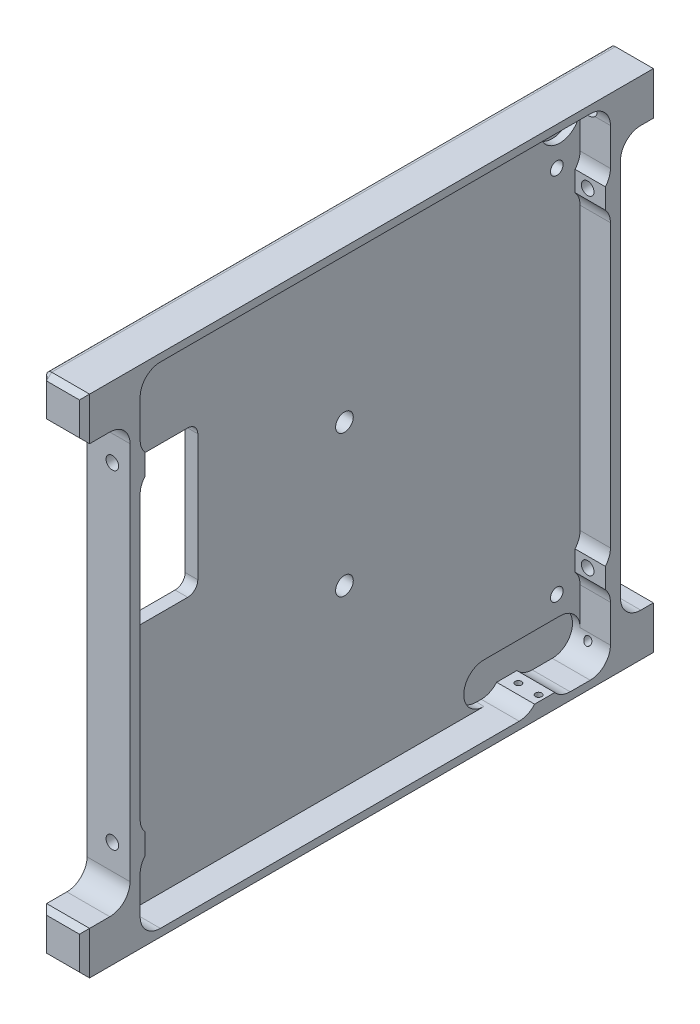
SolidWorks part; units mm, degrees
material "6061-T6 (SS)"
ref_plane "Front" through (0, 0, 0) normal (0, 0, 1) x (1, 0, 0)
ref_plane "Top" through (0, 0, 0) normal (0, 1, 0) x (1, 0, 0)
ref_plane "Right" through (0, 0, 0) normal (1, 0, 0) x (0, 0, -1)
sketch "Sketch1" plane through (0, 0, 0) normal (1, 0, 0) x (0, 0, -1)
  line L1 (0, 0) -> (-113.5, 0)
  line L2 (0, 0) -> (0, 100)
  line L3 (0, 100) -> (-113.5, 100)
  line L4 (-113.5, 0) -> (-113.5, 100)
  line L5 (-113.5, 91.5) -> (-104.5, 91.5)
  line L6 (-113.5, 91.5) -> (-113.5, 8.5)
  line L7 (-113.5, 8.5) -> (-104.5, 8.5)
  line L8 (-104.5, 91.5) -> (-104.5, 8.5)
  line L9 (0, 91.5) -> (-7.5, 91.5)
  line L10 (0, 91.5) -> (0, 8.5)
  line L11 (0, 8.5) -> (-7.5, 8.5)
  line L12 (-7.5, 91.5) -> (-7.5, 8.5)
  line L13 (-96.5, 91.5) -> (-15.5, 91.5)
  line L14 (-96.5, 91.5) -> (-96.5, 8.5)
  line L15 (-96.5, 8.5) -> (-15.5, 8.5)
  line L16 (-15.5, 91.5) -> (-15.5, 8.5)
  dimension "D1" = 113.5
  dimension "D2" = 100
  dimension "D3" = 8.5
  dimension "D4" = 8.5
  dimension "D5" = 8
  dimension "D6" = 8
  dimension "D7" = 9
  dimension "D8" = 7.5
extrude "Body" add sketch "Sketch1" along normal blind 8.5 contours L12 L9 L2 L3 L4 L5 L8 L7 L1 L11 L13 L16 L15 L14
fillet "RailFillet" radius 1 2 edges at (0, 0, 56.75) (0, 100, 56.75)
chamfer "FootChamfer" distance 1 angle 45 20 edges at (4.75, 0, 0) (8.5, 4.25, 0) (4.25, 8.5, 0) (0, 4.75, 0) (4.25, 91.5, 0) (8.5, 95.75, 0) (4.75, 100, 0) (0, 95.25, 0) (4.75, 100, 113.5) (8.5, 95.75, 113.5) (4.25, 91.5, 113.5) (0, 95.25, 113.5) (4.25, 8.5, 113.5) (8.5, 4.25, 113.5) (4.75, 0, 113.5) (0, 4.75, 113.5) (0.2929, 0.2929, 0) (0.2929, 99.7071, 0) (0.2929, 99.7071, 113.5) (0.2929, 0.2929, 113.5)
sketch "Sketch5" plane through (8.5, 0, 0) normal (1, 0, 0) x (0, 0, -1)
  line L1 (-96.5, 91.5) -> (-15.5, 91.5)
  line L2 (-96.5, 91.5) -> (-96.5, 8.5)
  line L3 (-96.5, 8.5) -> (-15.5, 8.5)
  line L4 (-15.5, 91.5) -> (-15.5, 8.5)
extrude "Boss-Extrude3" add sketch "Sketch5" against normal up to surface (8.5 mm away) up to face at (0, 50, 56.5)
sketch "Sketch6" plane through (8.5, 0, 0) normal (1, 0, 0) x (0, 0, -1)
  line L0 (-1, 100) -> (-112.5, 100) construction
  line L1 (-102.5, 98.5) -> (-9.5, 98.5)
  line L2 (-102.5, 98.5) -> (-102.5, 1.5)
  line L3 (-102.5, 1.5) -> (-9.5, 1.5)
  line L4 (-9.5, 98.5) -> (-9.5, 1.5)
  line L5 (-1, 0) -> (-112.5, 0) construction
  line L7 (-7.5, 91.5) -> (-7.5, 8.5) construction
  line L10 (-104.5, 91.5) -> (-104.5, 8.5) construction
  dimension "D1" = 1.5
  dimension "D2" = 1.5
  dimension "D3" = 2
  dimension "D4" = 2
extrude "Cut-Extrude3" cut sketch "Sketch6" against normal offset from surface (6 mm away) 2.5 up to face at (0, 50, 56.5)
sketch "Sketch4" plane through (8.5, 0, 0) normal (1, 0, 0) x (0, 0, -1)
  line L1 (-92.5, 90) -> (-19.5, 90)
  line L2 (-92.5, 90) -> (-92.5, 10)
  line L3 (-92.5, 10) -> (-19.5, 10)
  line L4 (-19.5, 90) -> (-19.5, 10)
  line L6 (-7.5, 91.5) -> (-7.5, 8.5) construction
  line L8 (-1, 100) -> (-112.5, 100) construction
  line L9 (-1, 0) -> (-112.5, 0) construction
  line L10 (-104.5, 91.5) -> (-104.5, 8.5) construction
  dimension "D1" = 12
  dimension "D2" = 10
  dimension "D3" = 10
  dimension "D4" = 12
ref_plane "Plane1" through (0, 50, 0) normal (0, 1, 0) x (1, 0, 0)
ref_plane "Plane2" through (0, 0, 56) normal (0, 0, -1) x (-1, 0, 0)
sketch "Sketch21" plane through (0, 0, 0) normal (1, 0, 0) x (0, 0, -1)
  line L0 (-98.1, 86.5) -> (-98.1, 13.5) construction
  line L1 (-98.1, 13.5) -> (-14.1, 13.5) construction
  line L2 (-14.1, 13.5) -> (-14.1, 86.5) construction
  line L3 (-14.1, 86.5) -> (-98.1, 86.5) construction
  line L4 (-14.1, 50) -> (-7.5, 50) construction
  line L6 (-7.5, 91.5) -> (-7.5, 8.5) construction
  line L7 (0, 99) -> (0, 92.5) construction
  line L8 (-14.1, 50) -> (-98.1, 50) construction
  line L9 (-56.1, 50) -> (-56.1, 36) construction
  line L10 (-7.5, 50) -> (-7.5, 0) construction
  line L11 (-112.5, 0) -> (-1, 0) construction
  line L12 (-1, 100) -> (-112.5, 100) construction
  line L13 (-7.5, 100) -> (-7.5, 50) construction
  line L16 (-56.1, 64) -> (-56.1, 50) construction
  point P3 (-14.1, 13.5)
  point P5 (-98.1, 86.5)
  point P7 (-98.1, 13.5)
  point P11 (-56.1, 36)
  point P25 (-14.1, 86.5)
  point P26 (-56.1, 64)
  dimension "D3" = 28
  dimension "D1" = 73
  dimension "D2" = 84
  dimension "D4" = 14.1
sketch "Sketch29" plane through (0, 0, 0) normal (0, 0, -1) x (-1, 0, 0)
  line L0 (-1, 92.5) -> (-7.5, 99)
  line L1 (-7.5, 99) -> (-1, 99)
  line L2 (-1, 99) -> (-4.25, 95.75)
hole_wizard "#8-36 Tapped Hole1" positions "Sketch30" profile "Sketch31" tap size "#8-36" standard "ANSI Inch"
sketch "Sketch30" plane through (0, 0, 0) normal (0, 0, -1) x (-1, 0, 0)
  point P0 (-4.25, 95.75)
sketch "Sketch31" plane through (4.25, 95.75, 0) normal (1, 0, 0) x (0, 1, 0)
  line L0 (0, 0) -> (0, 14.5878)
  line L1 (0, 14.5878) -> (1.7272, 13.55)
  line L2 (1.7272, 13.55) -> (1.7272, 0)
  line L5 (1.7272, 0) -> (0, 0)
  line L10 (0, 14.5878) -> (-1.7272, 13.55) construction
  line L11 (0, -6.35) -> (0, 107.95) construction
  dimension "Tap Drill Dia." = 3.4544
  dimension "Tap Drill Depth" = 13.55
  dimension "Drill Angle" = 118
cosmetic thread "Hole Thread1" parameters "D1"=10.5229, "D2"=4.1656
sketch "Sketch32" plane through (0, 0, 0) normal (0, 0, -1) x (-1, 0, 0)
  line L1 (-4.25, 1) -> (-4.25, 4.25) construction
  line L2 (-7.5, 1) -> (-1, 1) construction
  line L3 (-4.25, 4.25) -> (-7.5, 4.25) construction
  line L4 (-7.5, 7.5) -> (-7.5, 1) construction
  point P1 (-4.25, 4.25)
hole_wizard "#8-36 Tapped Hole2" [suppressed] positions "Sketch33" profile "Sketch34" tap size "#8-36" standard "ANSI Inch"
sketch "Sketch33" plane through (0, 0, 0) normal (0, 0, -1) x (-1, 0, 0)
  point P0 (-4.25, 4.25)
sketch "Sketch34" plane through (4.25, 4.25, 0) normal (1, 0, 0) x (0, 1, 0)
  line L0 (0, 0) -> (0, 11.4878)
  line L1 (0, 11.4878) -> (1.7272, 10.45)
  line L2 (1.7272, 10.45) -> (1.7272, 0)
  line L5 (1.7272, 0) -> (0, 0)
  line L10 (0, 11.4878) -> (-1.7272, 10.45) construction
  line L11 (0, -6.35) -> (0, 107.95) construction
  dimension "Tap Drill Dia." = 3.4544
  dimension "Tap Drill Depth" = 10.45
  dimension "Drill Angle" = 118
cosmetic thread "Hole Thread2" [suppressed] parameters "D1"=8.33, "D2"=4.1656
sketch "Sketch44" [suppressed] plane through (2.5, 0, 0) normal (1, 0, 0) x (0, 0, -1)
  point P0 (-17.45, 3.7)
  point P2 (-17.45, 7.7)
sketch "Sketch57" plane through (2.5, 0, 0) normal (1, 0, 0) x (0, 0, -1)
  line L0 (-9.5, 1.5) -> (-9.5, 98.5) construction
  line L1 (-9.5, 84.5) -> (-10.5, 84.5)
  line L2 (-9.5, 84.5) -> (-9.5, 80.5)
  line L3 (-9.5, 80.5) -> (-10.5, 80.5)
  line L4 (-10.5, 84.5) -> (-10.5, 80.5)
  line L5 (-102.5, 1.5) -> (-102.5, 98.5) construction
  line L6 (-9.5, 19.5) -> (-10.5, 19.5)
  line L7 (-9.5, 19.5) -> (-9.5, 15.5)
  line L8 (-9.5, 15.5) -> (-10.5, 15.5)
  line L9 (-10.5, 19.5) -> (-10.5, 15.5)
  line L10 (-10.5, 19.5) -> (-101.5, 19.5)
  line L11 (-10.5, 19.5) -> (-10.5, 15.5)
  line L12 (-10.5, 15.5) -> (-101.5, 15.5)
  line L13 (-101.5, 19.5) -> (-101.5, 15.5)
  line L14 (-10.5, 84.5) -> (-101.5, 84.5)
  line L15 (-10.5, 84.5) -> (-10.5, 80.5)
  line L16 (-10.5, 80.5) -> (-101.5, 80.5)
  line L17 (-101.5, 84.5) -> (-101.5, 80.5)
  line L18 (-101.5, 84.5) -> (-102.5, 84.5)
  line L19 (-101.5, 84.5) -> (-101.5, 80.5)
  line L20 (-101.5, 80.5) -> (-102.5, 80.5)
  line L21 (-102.5, 84.5) -> (-102.5, 80.5)
  line L22 (-9.5, 50) -> (-102.5, 50) construction
  line L23 (-101.5, 19.5) -> (-102.5, 19.5)
  line L24 (-101.5, 19.5) -> (-101.5, 15.5)
  line L25 (-101.5, 15.5) -> (-102.5, 15.5)
  line L26 (-102.5, 19.5) -> (-102.5, 15.5)
  line L28 (-102.5, 82.5) -> (-102.5, 50) construction
  line L29 (-102.5, 50) -> (-102.5, 17.5) construction
  line L31 (-9.5, 98.5) -> (-9.5, 1.5) construction
  dimension "D1" = 4
  dimension "D2" = 4
  dimension "D3" = 1
  dimension "D4" = 32.5
  dimension "D5" = 32.5
extrude "Boss-Extrude24" add sketch "Sketch57" along normal up to surface (6 mm away) contours L18 L21 L20 L17 | L23 L26 L25 L13 | L6 L9 L8 L7 | L1 L4 L3 L2 up to face at (8.5, 50, 56)
fillet "Fillet5" radius 4 8 edges at (5.5, 84.5, 102.5) (5.5, 19.5, 102.5) (5.5, 80.5, 102.5) (5.5, 15.5, 102.5) (5.5, 19.5, 9.5) (5.5, 15.5, 9.5) (5.5, 80.5, 9.5) (5.5, 84.5, 9.5)
sketch "Sketch59" plane through (0, 0, 7.5) normal (0, 0, -1) x (-1, 0, 0)
  line L0 (-5, 91.5) -> (-5, 82.5) construction
  line L2 (-5, 82.5) -> (-5, 17.5) construction
  line L3 (-5, 17.5) -> (-5, 8.5) construction
  line L5 (0, 91.5) -> (0, 8.5) construction
  line L6 (-8.5, 91.5) -> (0, 91.5) construction
  line L7 (-8.5, 8.5) -> (0, 8.5) construction
  dimension "D1" = 65
  dimension "D2" = 5
hole_wizard "M3x0.5 Tapped Hole1" positions "Sketch60" profile "Sketch61" tap size "M3x0.5" standard "ANSI Metric" end condition through all
sketch "Sketch60" plane through (0, 0, 7.5) normal (0, 0, -1) x (-1, 0, 0)
  point P0 (-5, 82.5)
  point P3 (-5, 17.5)
sketch "Sketch61" plane through (5, 82.5, 7.5) normal (1, 0, 0) x (0, 1, 0)
  line L0 (0, 0) -> (0, 106)
  line L1 (0, 106) -> (1.25, 106)
  line L2 (1.25, 106) -> (1.25, 0)
  line L5 (1.25, 0) -> (0, 0)
  line L11 (0, -6.35) -> (0, 107.95) construction
  dimension "Thru Tap Drill Dia." = 2.5
  dimension "Thru Tap Drill Depth" = 106
cosmetic thread "Hole Thread5" parameters "D2"=3
cosmetic thread "Hole Thread6" parameters "D2"=3
sketch "Sketch62" [suppressed] plane through (1, 0, 0) normal (1, 0, 0) x (0, 0, -1)
  line L1 (-11.25, 13.5) -> (-11.25, 1.5)
  line L2 (-11.5, 1.5) -> (-100, 1.5) construction
  line L3 (-11.25, 1.5) -> (-15.75, 1.5)
  line L4 (-15.75, 1.5) -> (-15.75, 10.1459)
  circle A0 centre (-14.75, 86.5) radius 3.5
  circle A1 centre (-14.75, 13.5) radius 3.5
  circle A2 centre (-97.75, 13.5) radius 3.5
  circle A3 centre (-97.75, 86.5) radius 3.5
  circle A4 centre (-97.75, 86.5) radius 1.25 construction
  circle A5 centre (-97.75, 13.5) radius 1.25 construction
  circle A6 centre (-14.75, 13.5) radius 1.25 construction
  circle A7 centre (-14.75, 86.5) radius 1.25 construction
  circle A8 centre (-97.75, 86.5) radius 1.25
  circle A9 centre (-97.75, 13.5) radius 1.25
  circle A10 centre (-14.75, 13.5) radius 1.25
  circle A11 centre (-14.75, 86.5) radius 1.25
  dimension "D1" = 7
  dimension "D2" = 4.5
fillet "Fillet7" radius 4 4 edges at (5.5, 98.5, 102.5) (5.5, 1.5, 102.5) (5.5, 1.5, 9.5) (5.5, 98.5, 9.5)
hole_wizard "M3x0.5 Tapped Hole2" positions "Sketch67" profile "Sketch68" tap size "M3x0.5" standard "ANSI Metric"
sketch "Sketch67" plane through (0, 0, 0) normal (-1, 0, 0) x (0, 0, 1)
  point P0 (14.1, 13.5)
  point P3 (14.1, 86.5)
  point P12 (98.1, 86.5)
  point P15 (98.1, 13.5)
  point P19 (0, 0)
  point P20 (0, 0)
sketch "Sketch68" plane through (0, 13.5, 14.1) normal (0, 1, 0) x (0, 0, 1)
  line L0 (0, 0) -> (0, 8.2511)
  line L1 (0, 8.2511) -> (1.25, 7.5)
  line L2 (1.25, 7.5) -> (1.25, 0)
  line L5 (1.25, 0) -> (0, 0)
  line L10 (0, 8.2511) -> (-1.25, 7.5) construction
  line L11 (0, -6.35) -> (0, 107.95) construction
  dimension "Tap Drill Dia." = 2.5
  dimension "Tap Drill Depth" = 7.5
  dimension "Drill Angle" = 118
cosmetic thread "Hole Thread17" parameters "D1"=2.5, "D2"=3
cosmetic thread "Hole Thread18" parameters "D1"=2.5, "D2"=3
cosmetic thread "Hole Thread21" parameters "D1"=2.5, "D2"=3
cosmetic thread "Hole Thread22" parameters "D1"=2.5, "D2"=3
fillet "Fillet8" radius 4 4 edges at (4.25, 8.5, 104.5) (4.25, 91.5, 104.5) (4.25, 8.5, 7.5) (4.25, 91.5, 7.5)
sketch "Sketch70" plane through (2.5, 0, 0) normal (1, 0, 0) x (0, 0, -1)
  line L0 (-13.5, 1.5) -> (-98.5, 1.5) construction
  line L2 (-13.5, 9.5) -> (-28.5, 9.5)
  line L4 (-13.5, 5.5) -> (-28.5, 5.5) construction
  line L5 (-28.5, 1.5) -> (-13.5, 1.5)
  circle A0 centre (-13.5, 94.5) radius 4
  arc A1 (-9.5, 94.5) -> (-13.5, 98.5) centre (-13.5, 94.5) ccw construction
  circle A2 centre (-13.5, 5.5) radius 4
  circle A3 centre (-28.5, 5.5) radius 4
  dimension "D1" = 15
extrude "Cut-Extrude14" cut sketch "Sketch70" against normal blind 1.5
sketch "Sketch75" plane through (0, 1.5, 0) normal (0, 1, 0) x (1, 0, 0)
  line L0 (1, -28.5) -> (1, -13.5) construction
  line L1 (1, -20.5) -> (8.5, -20.5)
  line L2 (1, -20.5) -> (1, -24.5)
  line L3 (1, -24.5) -> (8.5, -24.5)
  line L4 (8.5, -20.5) -> (8.5, -24.5)
  line L5 (8.5, -98.5) -> (8.5, -13.5) construction
  line L6 (8.5, -13.5) -> (1, -13.5) construction
  dimension "D1" = 7
  dimension "D2" = 4
extrude "Boss-Extrude25" add sketch "Sketch75" along normal blind 1.4
sketch "Sketch71" plane through (0, 2.9, 0) normal (0, 1, 0) x (1, 0, 0)
  line L0 (3.3, -22.5) -> (7.3, -22.5) construction
  line L1 (1, -28.5) -> (1, -24.5) construction
  dimension "D1" = 4
  dimension "D2" = 2.3
  dimension "D3" = 9
hole_wizard "M1.6x0.35 Tapped Hole1" positions "Sketch72" profile "Sketch73" tap size "M1.6x0.35" standard "ANSI Metric"
sketch "Sketch72" plane through (0, 2.9, 0) normal (0, 1, 0) x (1, 0, 0)
  point P0 (3.3, -22.5)
  point P3 (7.3, -22.5)
sketch "Sketch73" plane through (3.3, 2.9, 22.5) normal (1, 0, 0) x (0, 0, 1)
  line L0 (0, 0) -> (0, 4.6255)
  line L1 (0, 4.6255) -> (0.625, 4.25)
  line L2 (0.625, 4.25) -> (0.625, 0)
  line L5 (0.625, 0) -> (0, 0)
  line L10 (0, 4.6255) -> (-0.625, 4.25) construction
  line L11 (0, -6.35) -> (0, 107.95) construction
  dimension "Tap Drill Dia." = 1.25
  dimension "Tap Drill Depth" = 4.25
  dimension "Drill Angle" = 118
cosmetic thread "Hole Thread15" parameters "D1"=1.5, "D2"=1.6
cosmetic thread "Hole Thread16" parameters "D1"=1.5, "D2"=1.6
fillet "Fillet9" radius 4 2 edges at (4.75, 1.5, 24.5) (4.75, 1.5, 20.5)
sketch "Sketch76" plane through (0, 0, 0) normal (0, 0, -1) x (-1, 0, 0)
  line L0 (-1, 7.5) -> (-7.5, 1) construction
  point P4 (-4.25, 4.25)
hole_wizard "Ø1.5mm Dowel Hole1" positions "Sketch77" profile "Sketch79" hole size "Ø1.5" standard "ANSI Metric" end condition up to next
sketch "Sketch77" plane through (0, 0, 0) normal (0, 0, -1) x (-1, 0, 0)
  point P0 (-4.25, 4.25)
sketch "Sketch79" plane through (4.25, 4.25, 0) normal (1, 0, 0) x (0, 1, 0)
  line L0 (0, 0) -> (0, 9.7003)
  line L1 (0, 9.7003) -> (0.75, 9.7003)
  line L2 (0.75, 9.7003) -> (0.75, 0)
  line L5 (0.75, 0) -> (0, 0)
  line L11 (0, -6.35) -> (0, 107.95) construction
  dimension "Thru Hole Dia." = 1.5
  dimension "Thru Hole Depth" = 9.7003
sketch "Sketch81" plane through (2.5, 0, 0) normal (1, 0, 0) x (0, 0, -1)
  line L0 (-87.1, 51.5) -> (-87.1, 76.5) construction
  line L1 (-89.1, 51.5) -> (-89.1, 76.5)
  line L2 (-85.1, 51.5) -> (-85.1, 76.5)
  line L3 (-100.5, 51.5) -> (-100.5, 76.5) construction
  line L4 (-102.5, 51.5) -> (-102.5, 76.5)
  line L5 (-98.5, 51.5) -> (-98.5, 76.5)
  line L6 (-87.1, 51.5) -> (-100.5, 51.5) construction
  line L7 (-87.1, 49.5) -> (-100.5, 49.5)
  line L8 (-87.1, 76.5) -> (-100.5, 76.5) construction
  line L9 (-87.1, 78.5) -> (-100.5, 78.5)
  line L10 (-102.5, 22.1458) -> (-102.5, 77.8542) construction
  arc A0 (-89.1, 51.5) -> (-85.1, 51.5) centre (-87.1, 51.5) ccw
  arc A1 (-85.1, 76.5) -> (-89.1, 76.5) centre (-87.1, 76.5) ccw
  arc A2 (-102.5, 51.5) -> (-98.5, 51.5) centre (-100.5, 51.5) ccw
  arc A3 (-98.5, 76.5) -> (-102.5, 76.5) centre (-100.5, 76.5) ccw
  circle A6 centre (-98.1, 86.5) radius 1.25 construction
  point P2 (-87.1, 64)
  point P7 (-100.5, 64)
  line M19 (-102.5, 77.8542) -> (-102.5, 22.1458)
  dimension "D2" = 2
  dimension "D3" = 2
  dimension "D5" = 10
  dimension "D1" = 11
  dimension "D4" = 25
extrude "Cut-Extrude15" cut sketch "Sketch81" against normal through all contours L5 A3 A2 M19 | L2 A1 L1 A0 | A3 L5 A2 L7 A0 L1 A1 L9
sketch "Sketch84" plane through (0, 0, 0) normal (-1, 0, 0) x (0, 0, 1)
  line L0 (112.5, 0) -> (1, 0) construction
  line L1 (7.5, 87.5) -> (7.5, 12.5) construction
  circle A0 centre (56.1, 36) radius 1.75
  circle A1 centre (56.1, 64) radius 1.75
  point P8 (0, 0)
  dimension "D1" = 3.5
  dimension "D4" = 64
  dimension "D2" = 36
  dimension "D3" = 48.6
extrude "Cut-Extrude17" cut sketch "Sketch84" against normal through all
